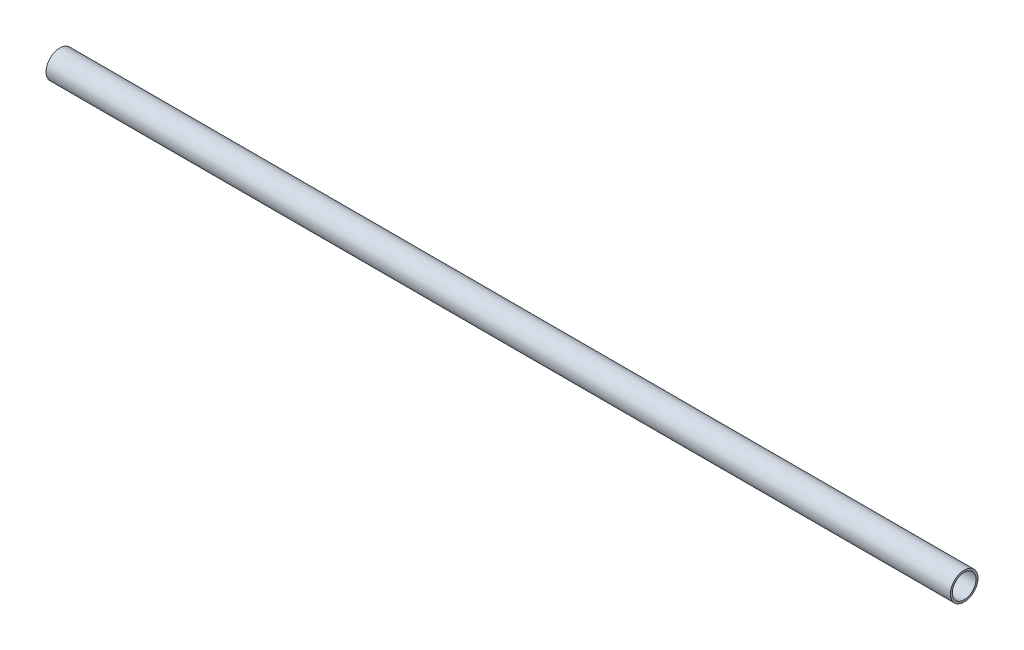
SolidWorks part; units mm, degrees
material "Thornel Mat VMA"
ref_plane "Ön Düzlem" through (0, 0, 0) normal (0, 0, 1) x (1, 0, 0)
ref_plane "Üst Düzlem" through (0, 0, 0) normal (0, 1, 0) x (1, 0, 0)
ref_plane "Sağ Düzlem" through (0, 0, 0) normal (1, 0, 0) x (0, 0, -1)
sketch "Çizim1" plane through (0, 0, 0) normal (1, 0, 0) x (0, 0, -1)
  circle A0 centre (0, 0) radius 7
  circle A1 centre (0, 0) radius 6
  dimension "D1" = 14
  dimension "D2" = 12
extrude "Yükseklik-Ekstrüzyon1" add sketch "Çizim1" along normal mid plane 458
sketch "Çizim2" plane through (229, 0, 0) normal (1, 0, 0) x (0, 0, -1)
  line L0 (0, -7) -> (0, 7) construction
  circle A0 centre (0, 0) radius 7 construction
  point P7 (0, 0)
